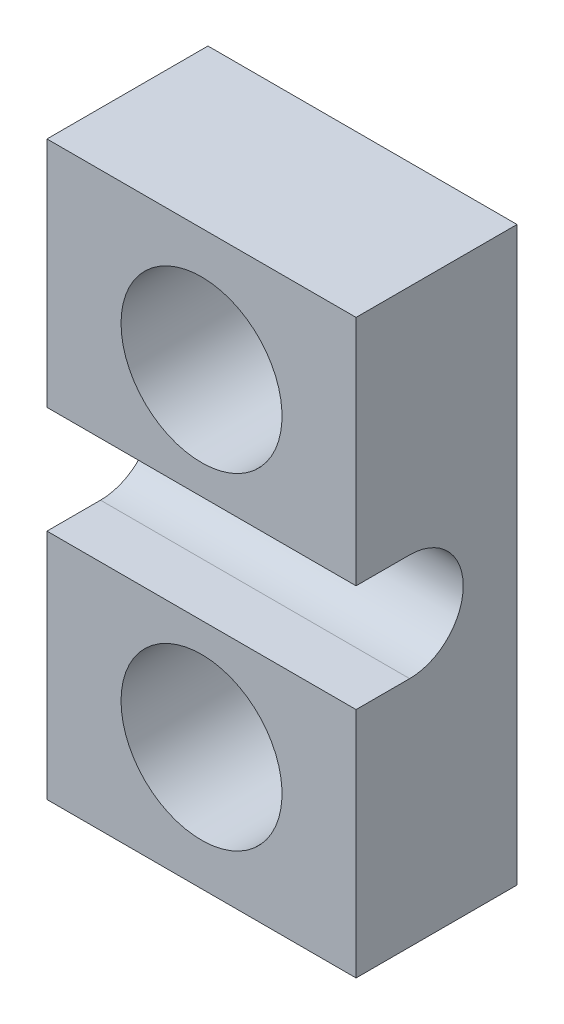
SolidWorks part; units mm, degrees
ref_plane "Front Plane" through (0, 0, 0) normal (0, 0, 1) x (1, 0, 0)
ref_plane "Top Plane" through (0, 0, 0) normal (0, 1, 0) x (1, 0, 0)
ref_plane "Right Plane" through (0, 0, 0) normal (1, 0, 0) x (0, 0, -1)
sketch "Sketch1" plane through (0, 0, 0) normal (0, 0, 1) x (1, 0, 0)
  line L1 (216.551, 143.9246) -> (210.4061, 143.9246)
  line L2 (216.551, 143.9246) -> (216.551, 132.5512)
  line L3 (216.551, 132.5512) -> (210.4061, 132.5512)
  line L4 (210.4061, 143.9246) -> (210.4061, 132.5512)
extrude "Boss-Extrude1" add sketch "Sketch1" along normal blind 3.2
sketch "Sketch2" plane through (0, 0, 0) normal (0, 0, -1) x (-1, 0, 0)
  line L0 (-213.4785, 141.4879) -> (-213.4785, 134.9879) construction
  line L1 (-213.4785, 141.4879) -> (-213.4785, 143.9246) construction
  line L2 (-216.551, 143.9246) -> (-210.4061, 143.9246) construction
  line L3 (-213.4785, 134.9879) -> (-213.4785, 132.5512) construction
  line L4 (-210.4061, 132.5512) -> (-216.551, 132.5512) construction
  circle A0 centre (-213.4785, 141.4879) radius 1.6
  circle A1 centre (-213.4785, 134.9879) radius 1.6
  dimension "D1" = 3.2
  dimension "D2" = 6.5
extrude "Cut-Extrude1" cut sketch "Sketch2" against normal through all
sketch "Sketch3" plane through (216.551, 0, 0) normal (1, 0, 0) x (0, 0, -1)
  line L0 (-3.2, 138.2379) -> (0, 138.2379) construction
  line L1 (-3.2, 132.5512) -> (-3.2, 143.9246) construction
  line L2 (-2.135, 137.1729) -> (-3.2, 137.1729)
  line L3 (0, 132.5512) -> (0, 143.9246) construction
  line L4 (-2.135, 139.3029) -> (-3.2, 139.3029)
  line L5 (-3.2, 137.1729) -> (-3.2, 139.3029)
  arc A0 (-2.135, 137.1729) -> (-2.135, 139.3029) centre (-2.135, 138.2379) ccw
  dimension "D1" = 2.13
extrude "Cut-Extrude2" cut sketch "Sketch3" against normal through all
